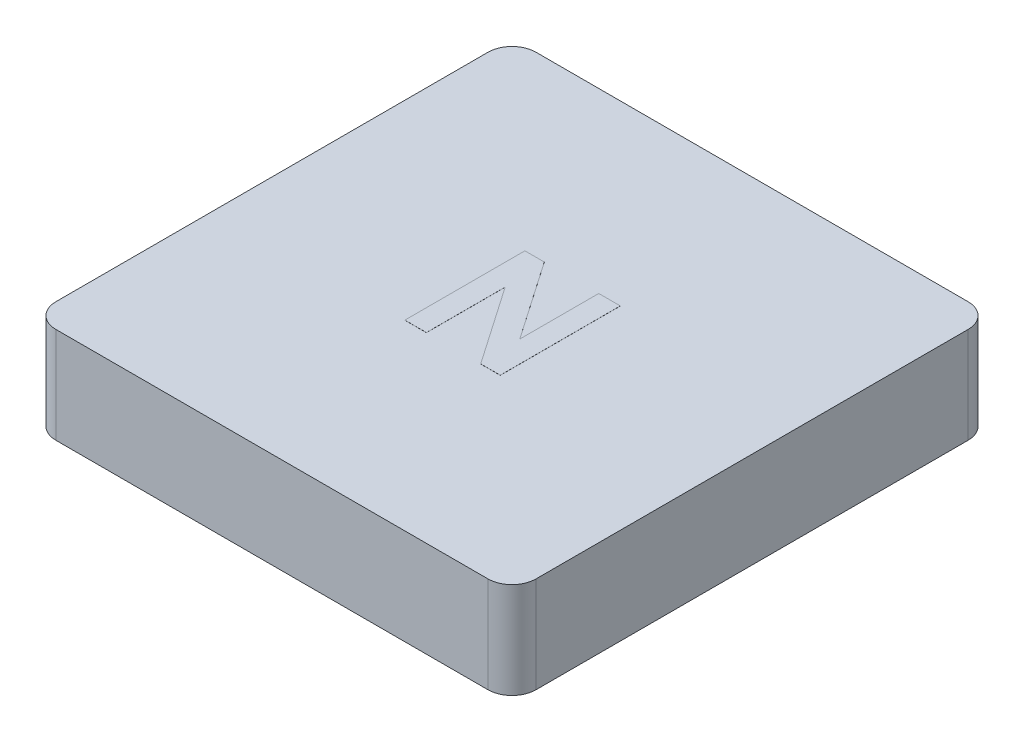
SolidWorks part; units mm, degrees
ref_plane "Front Plane" through (0, 0, 0) normal (0, 0, 1) x (1, 0, 0)
ref_plane "Top Plane" through (0, 0, 0) normal (0, 1, 0) x (1, 0, 0)
ref_plane "Right Plane" through (0, 0, 0) normal (1, 0, 0) x (0, 0, -1)
sketch "Sketch1" plane through (0, 0, 0) normal (0, 1, 0) x (1, 0, 0)
  line L0 (0, 0) -> (12.7, 0)
  line L1 (12.7, 0) -> (12.7, 12.7)
  line L2 (12.7, 12.7) -> (0, 12.7)
  line L3 (0, 12.7) -> (0, 0)
  dimension "D1" = 12.7
  dimension "D2" = 12.7
extrude "Boss-Extrude1" add sketch "Sketch1" along normal blind 2.54
fillet "Fillet1" radius 0.635 4 edges at (0, 1.27, -12.7) (12.7, 1.27, -12.7) (12.7, 1.27, 0) (0, 1.27, 0)
shell "Shell1" thickness 0.635 removed face at (6.35, 0, -6.35)
sketch "Sketch2" plane through (0, 1.905, 0) normal (0, -1, 0) x (-1, 0, 0)
  line L0 (-0.635, 6.35) -> (-12.065, 6.35) construction
  line L1 (-0.635, 12.065) -> (-0.635, 0.635) construction
  line L2 (-12.065, 0.635) -> (-12.065, 12.065) construction
  line L3 (-6.35, 0.635) -> (-6.35, 12.065) construction
  line L4 (-0.635, 0.635) -> (-12.065, 0.635) construction
  line L5 (-12.065, 12.065) -> (-0.635, 12.065) construction
  circle A0 centre (-6.35, 6.35) radius 2.54
  dimension "D1" = 5.08
extrude "Boss-Extrude2" add sketch "Sketch2" along normal up to surface (1.905 mm away) up to face at (6.35, 0, -6.35)
sketch "Sketch3" plane through (0, 2.54, 0) normal (0, 1, 0) x (1, 0, 0)
  line L0 (0, 12.065) -> (0, 0.635) construction
  line L1 (0.635, 0) -> (12.065, 0) construction
  text T0 "<b>N</b>"
  point P1 (0, 0)
  dimension "D1" = 4.6736
  dimension "D2" = 4.826
extrude "Boss-Extrude3" add sketch "Sketch3" along normal blind 0.0025
